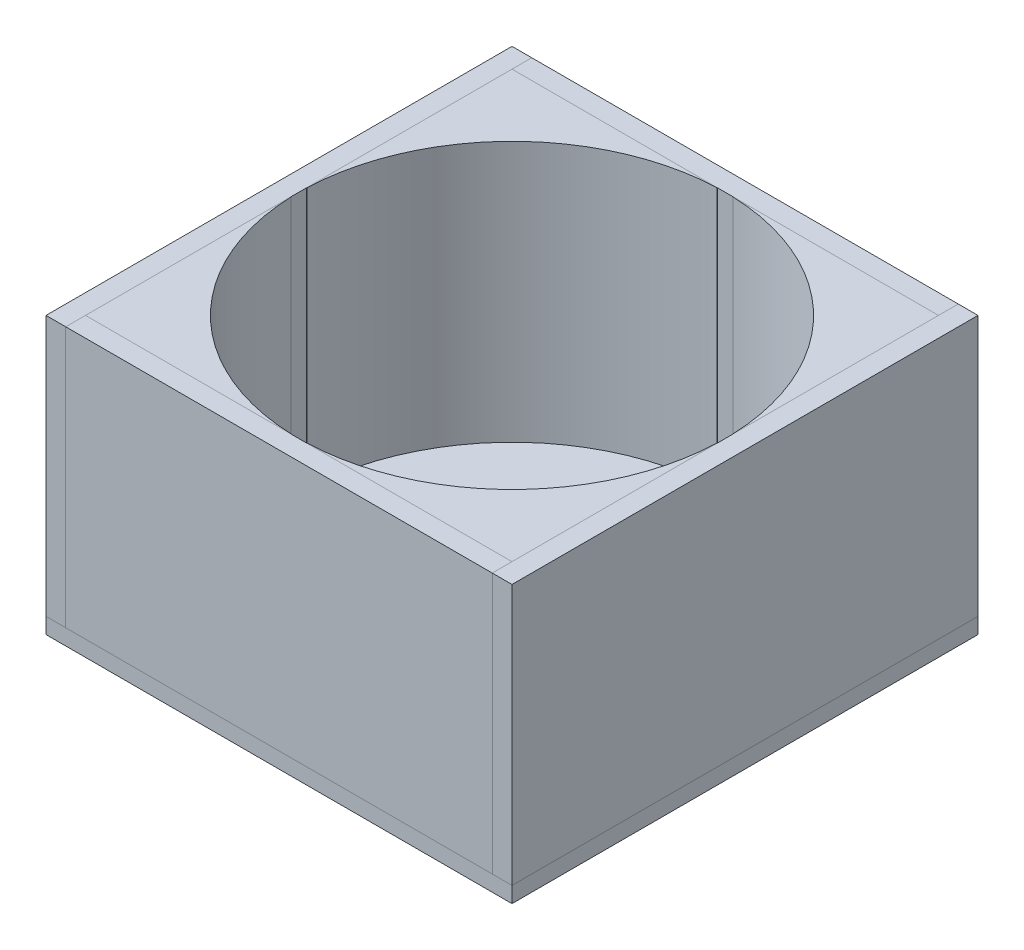
SolidWorks part; units mm, degrees
material "NEOPRENE"
ref_plane "Front" through (0, 0, 0) normal (0, 0, 1) x (1, 0, 0)
ref_plane "Top" through (0, 0, 0) normal (0, 1, 0) x (1, 0, 0)
ref_plane "Right" through (0, 0, 0) normal (1, 0, 0) x (0, 0, -1)
sketch "Sketch1" plane through (0, 0, 0) normal (0, 1, 0) x (1, 0, 0)
  line L1 (-685.8, 685.8) -> (685.8, 685.8) construction
  line L2 (-685.8, 685.8) -> (-685.8, -685.8) construction
  line L3 (-685.8, -685.8) -> (685.8, -685.8) construction
  line L4 (685.8, 685.8) -> (685.8, -685.8) construction
  line L5 (-685.8, 685.8) -> (685.8, -685.8) construction
  line L6 (-685.8, -685.8) -> (685.8, 685.8) construction
  line L7 (-685.8, 685.8) -> (685.8, 685.8)
  line L8 (-685.8, 685.8) -> (-685.8, 749.3)
  line L9 (-685.8, 749.3) -> (685.8, 749.3)
  line L10 (685.8, 685.8) -> (685.8, 749.3)
  line L11 (-685.8, -685.8) -> (685.8, -685.8)
  line L12 (-685.8, -685.8) -> (-685.8, -749.3)
  line L13 (-685.8, -749.3) -> (685.8, -749.3)
  line L14 (685.8, -685.8) -> (685.8, -749.3)
  point P0 (0, 0)
  dimension "D1" = 1371.6
  dimension "D2" = 1371.6
  dimension "D3" = 63.5
extrude "Boss-Extrude1" add sketch "Sketch1" along normal blind 838.2
sketch "Sketch2" plane through (0, 0, 0) normal (0, 1, 0) x (1, 0, 0)
  line L0 (-685.8, -749.3) -> (685.8, -749.3) construction
  line L1 (685.8, 749.3) -> (749.3, 749.3)
  line L2 (685.8, 749.3) -> (685.8, -749.3)
  line L3 (685.8, -749.3) -> (749.3, -749.3)
  line L4 (749.3, 749.3) -> (749.3, -749.3)
  line L5 (-685.8, 749.3) -> (-685.8, 685.8) construction
  line L7 (-685.8, 749.3) -> (-749.3, 749.3)
  line L8 (-685.8, 749.3) -> (-685.8, -749.3)
  line L9 (-685.8, -749.3) -> (-749.3, -749.3)
  line L10 (-749.3, 749.3) -> (-749.3, -749.3)
extrude "Boss-Extrude2" add sketch "Sketch2" along normal up to surface (838.2 mm away) separate body up to face at (0, 838.2, -717.55)
sketch "Sketch3" plane through (0, 0, 0) normal (0, -1, 0) x (1, 0, 0)
  line L0 (749.3, 749.3) -> (749.3, -749.3) construction
  line L1 (749.3, -749.3) -> (-749.3, -749.3)
  line L2 (749.3, -749.3) -> (749.3, 749.3)
  line L3 (749.3, 749.3) -> (-749.3, 749.3)
  line L4 (-749.3, -749.3) -> (-749.3, 749.3)
extrude "Boss-Extrude3" add sketch "Sketch3" along normal blind 50.8 separate body
sketch "Sketch4" plane through (0, 0, 0) normal (0, 1, 0) x (1, 0, 0)
  line L0 (685.8, -749.3) -> (685.8, 749.3) construction
  line L1 (685.8, -685.8) -> (685.8, -25.4)
  line L2 (685.8, -685.8) -> (-685.8, -685.8) construction
  line L3 (685.8, -685.8) -> (25.4, -685.8)
  line L4 (-685.8, 749.3) -> (-685.8, -749.3) construction
  line L5 (-685.8, 685.8) -> (-685.8, 25.4)
  line L6 (-685.8, 685.8) -> (685.8, 685.8) construction
  line L7 (-685.8, 685.8) -> (-25.4, 685.8)
  line L8 (0, -749.3) -> (0, 749.3) construction
  line L9 (-685.8, -749.3) -> (685.8, -749.3) construction
  line L10 (685.8, 749.3) -> (-685.8, 749.3) construction
  line L11 (749.3, 0) -> (-749.3, 0) construction
  line L12 (749.3, 749.3) -> (749.3, -749.3) construction
  line L13 (-749.3, -749.3) -> (-749.3, 749.3) construction
  line L14 (685.8, 25.4) -> (25.4, 25.4) construction
  line L15 (25.4, -685.8) -> (25.4, -25.4) construction
  line L16 (685.8, -25.4) -> (25.4, -25.4) construction
  line L17 (-25.4, -685.8) -> (-25.4, -25.4) construction
  line L18 (749.3, -25.4) -> (-749.3, -25.4) construction
  line L19 (749.3, 25.4) -> (-749.3, 25.4) construction
  line L20 (25.4, -749.3) -> (25.4, 749.3) construction
  line L21 (-25.4, -749.3) -> (-25.4, 749.3) construction
  line L22 (25.4, 685.8) -> (685.8, 685.8)
  line L23 (685.8, 25.4) -> (685.8, 685.8)
  line L24 (-25.4, -685.8) -> (-685.8, -685.8)
  line L25 (-685.8, -25.4) -> (-685.8, -685.8)
  line L26 (-25.4, 25.4) -> (-25.4, 685.8) construction
  line L27 (-25.4, 25.4) -> (-685.8, 25.4) construction
  line L28 (25.4, 25.4) -> (25.4, 685.8) construction
  line L29 (-25.4, -25.4) -> (-685.8, -25.4) construction
  line L30 (685.3295, 25.4) -> (685.8, 25.4)
  line L31 (685.3295, -25.4) -> (685.8, -25.4)
  line L32 (25.4, -685.3295) -> (25.4, -685.8)
  line L33 (-25.4, -685.3295) -> (-25.4, -685.8)
  line L34 (-685.8, -25.4) -> (-685.3295, -25.4)
  line L35 (-685.3295, 25.4) -> (-685.8, 25.4)
  line L36 (-25.4, 685.8) -> (-25.4, 685.3295)
  line L37 (25.4, 685.8) -> (25.4, 685.3295)
  arc A0 (-25.4, 685.3295) -> (-685.3295, 25.4) centre (0, 0) ccw
  arc A1 (685.3295, 25.4) -> (25.4, 685.3295) centre (0, 0) ccw
  arc A2 (25.4, -685.3295) -> (685.3295, -25.4) centre (0, 0) ccw
  arc A3 (-685.3295, -25.4) -> (-25.4, -685.3295) centre (0, 0) ccw
  dimension "D1" = 25.4
  dimension "D2" = 25.4
extrude "Boss-Extrude4" add sketch "Sketch4" along normal blind 838.2 separate body
